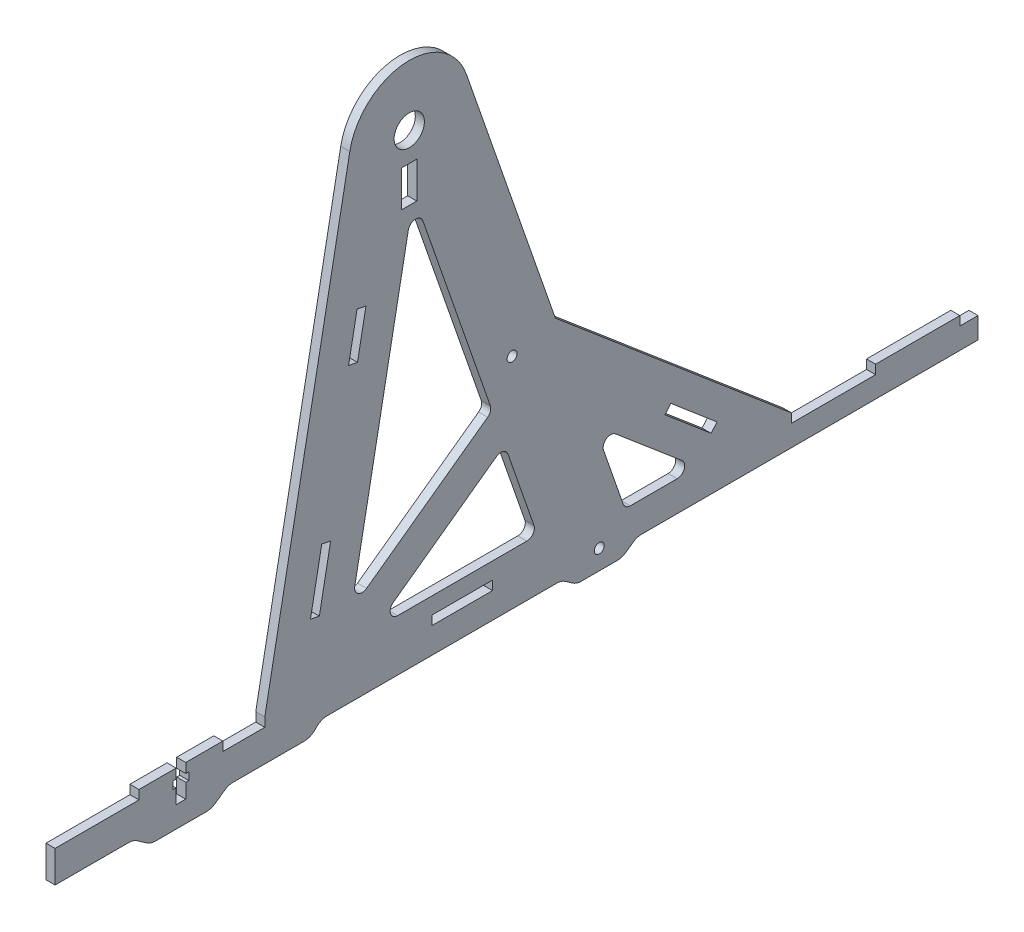
SolidWorks part; units mm, degrees
ref_plane "Front Plane" through (0, 0, 0) normal (0, 0, 1) x (1, 0, 0)
ref_plane "Top Plane" through (0, 0, 0) normal (0, 1, 0) x (1, 0, 0)
ref_plane "Right Plane" through (0, 0, 0) normal (1, 0, 0) x (0, 0, -1)
sketch "Sketch1" plane through (0, 0, 0) normal (1, 0, 0) x (0, 0, -1)
  line L0 (-152.5, 33) -> (152.5, 33)
  line L1 (152.5, 33) -> (152.5, 23)
  line L2 (-152.5, 33) -> (-152.5, -33)
  line L4 (107.5, 23) -> (152.5, 23)
  line L5 (57.5, -27) -> (57.5, -33)
  line L6 (57.5, -33) -> (-152.5, -33)
  arc A0 (57.5, -27) -> (107.5, 23) centre (107.5, -27) cw
  point P4 (-152.5, 0)
  point P7 (0, 33)
  dimension "D1" = 50
  dimension "D2" = 95
  dimension "D3" = 305
  dimension "D4" = 66
  dimension "D5" = 6
extrude "Boss-Extrude1" add sketch "Sketch1" along normal blind 3
sketch "Sketch2" plane through (3, 0, 0) normal (1, 0, 0) x (0, 0, -1)
  line L0 (-129.1567, -30) -> (-152.5, -30) construction
  line L1 (-129.1567, -30) -> (-105.8133, -30)
  line L2 (-129.1567, -30) -> (-129.1567, -27)
  line L3 (-129.1567, -27) -> (-105.8133, -27)
  line L4 (-105.8133, -30) -> (-105.8133, -27)
  line L5 (-129.1567, -30) -> (-105.8133, -27) construction
  line L6 (-129.1567, -27) -> (-105.8133, -30) construction
  line L7 (-82.47, -30) -> (-59.1266, -30)
  line L8 (-82.47, -30) -> (-82.47, -27)
  line L9 (-82.47, -27) -> (-59.1266, -27)
  line L10 (-59.1266, -30) -> (-59.1266, -27)
  line L11 (-82.47, -30) -> (-59.1266, -27) construction
  line L12 (-82.47, -27) -> (-59.1266, -30) construction
  line L13 (-35.7833, -30) -> (-12.4399, -30)
  line L14 (-35.7833, -30) -> (-35.7833, -27)
  line L15 (-35.7833, -27) -> (-12.4399, -27)
  line L16 (-12.4399, -30) -> (-12.4399, -27)
  line L17 (-35.7833, -30) -> (-12.4399, -27) construction
  line L18 (-35.7833, -27) -> (-12.4399, -30) construction
  line L19 (10.9034, -30) -> (34.2467, -30)
  line L20 (10.9034, -30) -> (10.9034, -27)
  line L21 (10.9034, -27) -> (34.2467, -27)
  line L22 (34.2467, -30) -> (34.2467, -27)
  line L23 (10.9034, -30) -> (34.2467, -27) construction
  line L24 (10.9034, -27) -> (34.2467, -30) construction
  line L25 (-152.5, 33) -> (-152.5, -33) construction
  line L26 (-105.8133, -30) -> (-82.47, -30) construction
  line L27 (-59.1266, -30) -> (-35.7833, -30) construction
  line L28 (-12.4399, -30) -> (10.9034, -30) construction
  line L29 (34.2467, -30) -> (57.5901, -30) construction
  line L30 (-152.5, -33) -> (57.5, -33) construction
  line L31 (152.5, 33) -> (-152.5, 33) construction
  line L36 (-152.5, 30) -> (-124.7727, 30)
  line L37 (-152.5, 30) -> (-152.5, 33)
  line L42 (-152.5, 33) -> (-124.7727, 33)
  line L43 (-124.7727, 30) -> (-124.7727, 33)
  line L44 (-149.5, 12) -> (-149.5, 30) construction
  line L45 (-152.5, 30) -> (-124.7727, 33) construction
  line L46 (-152.5, 33) -> (-124.7727, 30) construction
  line L47 (-149.5, -33) -> (-152.5, -33)
  line L52 (152.5, 23) -> (152.5, 33) construction
  line L53 (-97.0455, 30) -> (-69.3182, 30)
  line L54 (-97.0455, 30) -> (-97.0455, 33)
  line L55 (-97.0455, 33) -> (-69.3182, 33)
  line L56 (-69.3182, 30) -> (-69.3182, 33)
  line L57 (-97.0455, 30) -> (-69.3182, 33) construction
  line L58 (-97.0455, 33) -> (-69.3182, 30) construction
  line L59 (-41.5909, 30) -> (-13.8636, 30)
  line L60 (-41.5909, 30) -> (-41.5909, 33)
  line L61 (-41.5909, 33) -> (-13.8636, 33)
  line L62 (-13.8636, 30) -> (-13.8636, 33)
  line L63 (-41.5909, 30) -> (-13.8636, 33) construction
  line L64 (-41.5909, 33) -> (-13.8636, 30) construction
  line L65 (13.8636, 30) -> (41.5909, 30)
  line L66 (13.8636, 30) -> (13.8636, 33)
  line L67 (13.8636, 33) -> (41.5909, 33)
  line L68 (41.5909, 30) -> (41.5909, 33)
  line L69 (13.8636, 30) -> (41.5909, 33) construction
  line L70 (13.8636, 33) -> (41.5909, 30) construction
  line L71 (69.3182, 30) -> (97.0455, 30)
  line L72 (69.3182, 30) -> (69.3182, 33)
  line L73 (69.3182, 33) -> (97.0455, 33)
  line L74 (97.0455, 30) -> (97.0455, 33)
  line L75 (69.3182, 30) -> (97.0455, 33) construction
  line L76 (69.3182, 33) -> (97.0455, 30) construction
  line L77 (124.7727, 30) -> (152.5, 30)
  line L78 (124.7727, 30) -> (124.7727, 33)
  line L79 (124.7727, 33) -> (152.5, 33)
  line L80 (152.5, 30) -> (152.5, 33)
  line L81 (124.7727, 30) -> (152.5, 33) construction
  line L82 (124.7727, 33) -> (152.5, 30) construction
  line L83 (-124.7727, 30) -> (-97.0455, 30) construction
  line L84 (-69.3182, 30) -> (-41.5909, 30) construction
  line L85 (-13.8636, 30) -> (13.8636, 30) construction
  line L86 (41.5909, 30) -> (69.3182, 30) construction
  line L87 (97.0455, 30) -> (124.7727, 30) construction
  line L88 (-149.5, -33) -> (-149.5, -24)
  line L89 (-149.5, -24) -> (-152.5, -24)
  line L90 (-152.5, -33) -> (-152.5, -24)
  line L91 (-149.5, -33) -> (-152.5, -24) construction
  line L92 (-149.5, -24) -> (-152.5, -33) construction
  line L93 (-149.5, -6) -> (-152.5, -6)
  line L94 (-149.5, -6) -> (-149.5, 12)
  line L95 (-149.5, 12) -> (-152.5, 12)
  line L96 (-152.5, -6) -> (-152.5, 12)
  line L97 (-149.5, -6) -> (-152.5, 12) construction
  line L98 (-149.5, 12) -> (-152.5, -6) construction
  line L99 (-149.5, -6) -> (-149.5, -24) construction
  line L100 (146.5, 30) -> (146.5, 33)
  arc A0 (107.5, 23) -> (57.5, -27) centre (107.5, -27) ccw construction
  point P0 (-117.485, -28.5)
  point P5 (-70.7983, -28.5)
  point P10 (-24.1116, -28.5)
  point P15 (22.5751, -28.5)
  point P29 (-138.6364, 31.5)
  point P36 (-83.1818, 31.5)
  point P41 (-27.7273, 31.5)
  point P46 (27.7273, 31.5)
  point P51 (83.1818, 31.5)
  point P56 (138.6364, 31.5)
  point P61 (-151, 3)
  point P64 (-151, -28.5)
  line M15 (-152.5, 33) -> (-152.5, -33)
  line M16 (-152.5, -33) -> (57.5, -33)
  line M20 (152.5, 23) -> (152.5, 33)
  line M21 (152.5, 33) -> (-152.5, 33)
  dimension "D1" = 3
  dimension "D2" = 3
  dimension "D3" = 9
  dimension "D4" = 6
extrude "Cut-Extrude1" cut sketch "Sketch2" against normal through all both and the other way through all contours L36 L43 M21 M15 | L53 L56 L54 M21 | L59 L62 L60 M21 | L94 L95 L93 M15 | L88 L89 M15 M16 | L1 L4 L3 L2 | L7 L10 L9 L8 | L19 L22 L21 L20 | L100 L77 M20 M21 | L16 L15 L14 L13 region at (3, -28.5, 117.485) region at (3, -28.5, 70.7983) region at (3, -28.5, -22.5751) region at (3, 31.5, 138.6364) region at (3, 31.5, 27.7273) region at (3, 31.5, 83.1818) region at (3, -28.5, 151) region at (3, 3, 151) region at (3, 31.5, -149.5)
sketch "Sketch3" plane through (3, 0, 0) normal (1, 0, 0) x (0, 0, -1)
  line L0 (-97.0455, 33) -> (-124.7727, 33) construction
  line L1 (-112.5091, 22.5) -> (-109.3091, 22.5)
  line L2 (-112.5091, 22.5) -> (-112.5091, 33)
  line L3 (-112.5091, 33) -> (-109.3091, 33)
  line L4 (-109.3091, 22.5) -> (-109.3091, 33)
  line L5 (-112.5091, 22.5) -> (-109.3091, 33) construction
  line L6 (-112.5091, 33) -> (-109.3091, 22.5) construction
  line L21 (-113.5091, 29.825) -> (-108.3091, 29.825)
  line L22 (-113.5091, 29.825) -> (-113.5091, 27.325)
  line L23 (-113.5091, 27.325) -> (-108.3091, 27.325)
  line L24 (-108.3091, 29.825) -> (-108.3091, 27.325)
  line L25 (-113.5091, 29.825) -> (-108.3091, 27.325) construction
  line L26 (-113.5091, 27.325) -> (-108.3091, 29.825) construction
  line L27 (-110.9091, 29.825) -> (-110.9091, 33) construction
  point P0 (-110.9091, 27.75)
  point P19 (-110.9091, 28.575)
  point P24 (-110.9091, 33)
  dimension "D1" = 3.2
  dimension "D2" = 10.5
  dimension "D3" = 2.5
  dimension "D4" = 5.2
  dimension "D5" = 3.175
extrude "Cut-Extrude2" cut sketch "Sketch3" against normal through all both and the other way through all contours L4 L3 L2 L1 | L23 L24 L21 L22
fillet "Fillet1" radius 2.5 1 edges at (1.5, -33, -57.5)
sketch "Sketch4" plane through (0, 0, 0) normal (1, 0, 0) x (0, 0, -1)
  line L3 (-83.1818, 30) -> (35.8182, 30)
  line L4 (-13.8636, 30) -> (-41.5909, 30) construction
  line L5 (-69.3182, 30) -> (-97.0455, 30) construction
  line L6 (35.8182, 33) -> (-16.565, 183.5716)
  line L7 (146.5, 33) -> (-13.8636, 33) construction
  line L8 (-83.1818, 30) -> (-83.1818, 33)
  line L9 (-97.0455, 33) -> (-109.3091, 33) construction
  line L22 (-83.1818, 33) -> (-55.1028, 180.7344)
  line L23 (-46.975, 40) -> (-3.9299, 71.1677)
  line L24 (-149.5, -33) -> (55, -33) construction
  line L25 (35.8182, 30) -> (35.8182, 33)
  line L26 (-56.4038, 40) -> (-34.0336, 157.6985)
  line L27 (-34.0336, 157.6985) -> (6.9132, 40)
  line L28 (6.9132, 40) -> (-56.4038, 40)
  line L29 (-34.0336, 157.6985) -> (-10.4217, 165.9129) construction
  line L30 (-34.0336, 157.6985) -> (-58.5939, 162.3665) construction
  line L31 (12.8176, 99.1133) -> (90.8182, 33)
  line L32 (-54.6433, 49.263) -> (-8.047, 83.002)
  line L33 (25.753, 61.9315) -> (59.8865, 33)
  line L34 (25.753, 61.9315) -> (38.6847, 77.1884) construction
  line L35 (59.8865, 33) -> (90.8182, 33)
  line L36 (146.5, 33) -> (-13.8636, 33) construction
  line L37 (-54.6433, 49.263) -> (-56.4038, 40) construction
  line L38 (-46.975, 40) -> (-56.4038, 40) construction
  arc A0 (-55.1028, 180.7344) -> (-16.565, 183.5716) centre (-35.4545, 177) cw
  circle A1 centre (-35.4545, 177) radius 5
  point P40 (-83.1818, 30)
  dimension "D2" = 10
  dimension "D3" = 15
  dimension "D1" = 210
  dimension "D4" = 25
  dimension "D5" = 35.4545
  dimension "D6" = 119
  dimension "D7" = 10
  dimension "D8" = 20
  dimension "D9" = 70
  dimension "D10" = 55
  dimension "D11" = 12
  dimension "D12" = 33
extrude "Boss-Extrude2" add sketch "Sketch4" along normal up to surface (3 mm away) contours A1 | A0 L3 L25 L6 A1 | L33 L35 L31 L6 | L32 L26 L28 L23 L27 region at (0, 31.5, 81.1312) region at (0, 57.9734, -47.9055) region at (0, 59.827, 29.9332) region at (0, 177, 35.4545) up to face at (3, -28.5, 24.1116)
fillet "Fillet2" radius 2.5 9 edges at (1.5, 157.6985, 34.0336) (1.5, 40, -6.9132) (1.5, 61.9315, -25.753) (1.5, 33, -59.8865) (1.5, 33, -35.8182) (1.5, 49.263, 54.6433) (1.5, 83.002, 8.047) (1.5, 71.1677, 3.9299) (1.5, 40, 46.975)
ref_axis "Axis1" through (-68.2488, 177, 35.4545) along (1, 0, 0)
sketch "Sketch6" plane through (3, 0, 0) normal (1, 0, 0) x (0, 0, -1)
  line L0 (34.2467, -27) -> (10.9034, -27) construction
  line L1 (57.5, -30.5) -> (57.5, -27) construction
  line L2 (-35.4545, 177) -> (40.6474, -6) construction
  circle A0 centre (40.6474, -6) radius 9.6 construction
  circle A1 centre (-35.4545, 177) radius 38.4 construction
  circle A2 centre (27.3425, 25.9938) radius 25.05 construction
  circle A3 centre (-1.4929, 95.3336) radius 50.0466 construction
  circle A5 centre (-35.4545, 177) radius 5
  circle A6 centre (-1.4929, 95.3336) radius 1.65
  circle A7 centre (27.3425, 25.9938) radius 1.65
  arc A8 (-16.565, 183.5716) -> (-55.1028, 180.7344) centre (-35.4545, 177) ccw construction
  point P1 (40.6474, -6)
  point P5 (-1.4929, 95.3336)
  point P6 (27.3425, 25.9938)
  dimension "D3" = 19.2
  dimension "D4" = 76.8
  dimension "D5" = 50.1
  dimension "D6" = 3.3
  dimension "D7" = 10
  dimension "D1" = 21
  dimension "D2" = 16.8526
extrude "Cut-Extrude5" cut sketch "Sketch6" against normal through all both and the other way through all
sketch "Sketch8" plane through (0, 0, 0) normal (1, 0, 0) x (0, 0, -1)
  line L0 (-40, 0) -> (-5, 0) construction
  circle A0 centre (-5, 0) radius 10
  circle A1 centre (-40, 0) radius 10
  dimension "D1" = 20
  dimension "D2" = 35
  dimension "D3" = 5
extrude "Cut-Extrude6" cut sketch "Sketch8" against normal through all both and the other way through all
sketch "Sketch9" plane through (0, 0, 0) normal (1, 0, 0) x (0, 0, -1)
  line L0 (-68.1117, 53.3785) -> (-64.3772, 73.0268)
  line L1 (-68.1117, 53.3785) -> (-65.1644, 52.8184)
  line L2 (-64.3772, 73.0268) -> (-61.43, 72.4666)
  line L3 (-65.1644, 52.8184) -> (-61.43, 72.4666)
  line L4 (-68.1117, 53.3785) -> (-61.43, 72.4666) construction
  line L5 (-64.3772, 73.0268) -> (-65.1644, 52.8184) construction
  line L6 (-55.508, 119.6914) -> (-52.7072, 134.4276)
  line L7 (-55.508, 119.6914) -> (-52.5607, 119.1312)
  line L8 (-52.7072, 134.4276) -> (-49.7599, 133.8674)
  line L9 (-52.5607, 119.1312) -> (-49.7599, 133.8674)
  line L10 (-55.508, 119.6914) -> (-49.7599, 133.8674) construction
  line L11 (-52.7072, 134.4276) -> (-52.5607, 119.1312) construction
  line L12 (64.3114, 40.392) -> (49.0546, 53.3237)
  line L13 (64.3114, 40.392) -> (66.2512, 42.6805)
  line L14 (49.0546, 53.3237) -> (50.9943, 55.6122)
  line L15 (66.2512, 42.6805) -> (50.9943, 55.6122)
  line L16 (64.3114, 40.392) -> (50.9943, 55.6122) construction
  line L17 (49.0546, 53.3237) -> (66.2512, 42.6805) construction
  line L18 (-46.4222, 92.517) -> (-70.9826, 97.185) construction
  line L19 (-27.9315, 31.5) -> (-7.9315, 31.5)
  line L20 (-27.9315, 31.5) -> (-27.9315, 34.5)
  line L21 (-27.9315, 34.5) -> (-7.9315, 34.5)
  line L22 (-7.9315, 31.5) -> (-7.9315, 34.5)
  line L23 (-27.9315, 31.5) -> (-7.9315, 34.5) construction
  line L24 (-27.9315, 34.5) -> (-7.9315, 31.5) construction
  line L26 (-35.7791, 148.5145) -> (-53.4682, 55.4456) construction
  line L27 (-64.7708, 62.9226) -> (-52.6339, 126.7794) construction
  line L29 (90.8182, 33) -> (12.8176, 99.1133) construction
  line L30 (64.1187, 55.6305) -> (51.187, 40.3737) construction
  line L31 (54.687, 37.4071) -> (32.7403, 56.0091) construction
  line L32 (-17.9315, 40) -> (-17.9315, 33) construction
  line L33 (-39.2595, 40) -> (3.3965, 40) construction
  line L35 (-55.1028, 180.7344) -> (-83.1818, 33) construction
  point P0 (-17.9315, 33)
  point P1 (-64.7708, 62.9226)
  point P2 (-52.6339, 126.7794)
  point P3 (57.6529, 48.0021)
  point P26 (-58.7024, 94.851)
  point P27 (-58.7024, 94.851)
  point P38 (57.6529, 48.0021)
  dimension "D6" = 57
  dimension "D1" = 3
  dimension "D2" = 15
  dimension "D3" = 65
  dimension "D4" = 7
  dimension "D5" = 35
  dimension "D7" = 20
extrude "Cut-Extrude7" cut sketch "Sketch9" against normal through all both and the other way through all
sketch "Sketch10" plane through (0, 0, 0) normal (1, 0, 0) x (0, 0, -1)
  line L0 (-152.5, 30) -> (-152.5, 12) construction
  line L1 (152.5, -33) -> (-152.5, -33)
  line L2 (152.5, -33) -> (152.5, 19.5)
  line L3 (152.5, 19.5) -> (-152.5, 19.5)
  line L4 (-152.5, -33) -> (-152.5, 19.5)
  line L5 (152.5, -33) -> (-152.5, 19.5) construction
  line L6 (152.5, 19.5) -> (-152.5, -33) construction
  line L7 (-149.5, -33) -> (55, -33) construction
  line L8 (152.5, 23) -> (152.5, 30) construction
  line L9 (-109.3091, 22.5) -> (-112.5091, 22.5) construction
  line L10 (-68.1117, 22.9938) -> (152.5, 22.9938)
  line L11 (-68.1117, 22.9938) -> (-68.1117, 19.5)
  line L12 (-68.1117, 19.5) -> (152.5, 19.5)
  line L13 (152.5, 22.9938) -> (152.5, 19.5)
  line L14 (-68.1117, 22.9938) -> (152.5, 19.5) construction
  line L15 (-68.1117, 19.5) -> (152.5, 22.9938) construction
  line L16 (14.8529, 22.9938) -> (19.8425, 19.5)
  line L17 (39.8322, 22.9938) -> (34.8425, 19.5)
  line L18 (19.8425, 19.5) -> (34.8425, 19.5) construction
  line L19 (-68.1117, 19.5) -> (-64.6179, 22.9938)
  line L20 (-126.6217, 19.5) -> (-120.9091, 15.5)
  line L21 (-120.9091, 15.5) -> (-100.9091, 15.5)
  line L22 (-100.9091, 15.5) -> (-95.1965, 19.5)
  circle A1 centre (27.3425, 25.9938) radius 1.65 construction
  point P0 (0, -6.75)
  point P12 (42.1942, 21.2469)
  point P26 (27.3425, 25.9938)
  point P27 (27.3425, 19.5)
  point P29 (-110.9091, 15.5)
  point P33 (-110.9091, 22.5)
  dimension "D1" = 3
  dimension "D2" = 3
  dimension "D3" = 35
  dimension "D4" = 15
  dimension "D5" = 45
  dimension "D6" = 4
  dimension "D7" = 20
  dimension "D8" = 35
extrude "Cut-Extrude8" cut sketch "Sketch10" against normal through all both and the other way through all contours L4 L1 L2 L3 | L13 L10 L11 L3 | L16 L10 L11 L12 region at (0, -6.9077, -0.717) region at (0, 21.2343, -94.9097) region at (0, 21.2174, 24.5022)
sketch "Sketch11" plane through (0, 0, 0) normal (1, 0, 0) x (0, 0, -1)
  line L0 (146.5, 33) -> (90.8182, 33) construction
  line L1 (118.6591, 30) -> (90.8182, 30)
  line L2 (118.6591, 30) -> (118.6591, 33)
  line L3 (118.6591, 33) -> (90.8182, 33)
  line L4 (90.8182, 30) -> (90.8182, 33)
  line L5 (118.6591, 30) -> (90.8182, 33) construction
  line L6 (118.6591, 33) -> (90.8182, 30) construction
  line L7 (-83.1818, 30) -> (-97.0455, 30) construction
  point P0 (104.7386, 31.5)
  point P8 (118.6591, 33)
extrude "Cut-Extrude9" cut sketch "Sketch11" against normal through all both and the other way through all
fillet "Fillet3" radius 5 10 edges at (1.5, 22.9938, -39.8322) (1.5, 19.5, -34.8425) (1.5, 19.5, -19.8425) (1.5, 22.9938, -14.8529) (1.5, 19.5, 68.1117) (1.5, 22.9938, 64.6179) (1.5, 15.5, 120.9091) (1.5, 19.5, 126.6217) (1.5, 15.5, 100.9091) (1.5, 19.5, 95.1965)
sketch "Sketch12" plane through (3, 0, 0) normal (1, 0, 0) x (0, 0, -1)
  line L1 (-37.9545, 155.5) -> (-32.9545, 155.5)
  line L2 (-37.9545, 155.5) -> (-37.9545, 167.5)
  line L3 (-37.9545, 167.5) -> (-32.9545, 167.5)
  line L4 (-32.9545, 155.5) -> (-32.9545, 167.5)
  line L5 (-37.9545, 155.5) -> (-32.9545, 167.5) construction
  line L6 (-37.9545, 167.5) -> (-32.9545, 155.5) construction
  point P0 (-35.4545, 161.5)
  point P5 (-35.4545, 177)
  dimension "D1" = 5
  dimension "D2" = 12
  dimension "D3" = 15.5
extrude "Cut-Extrude10" cut sketch "Sketch12" against normal through all both and the other way through all
